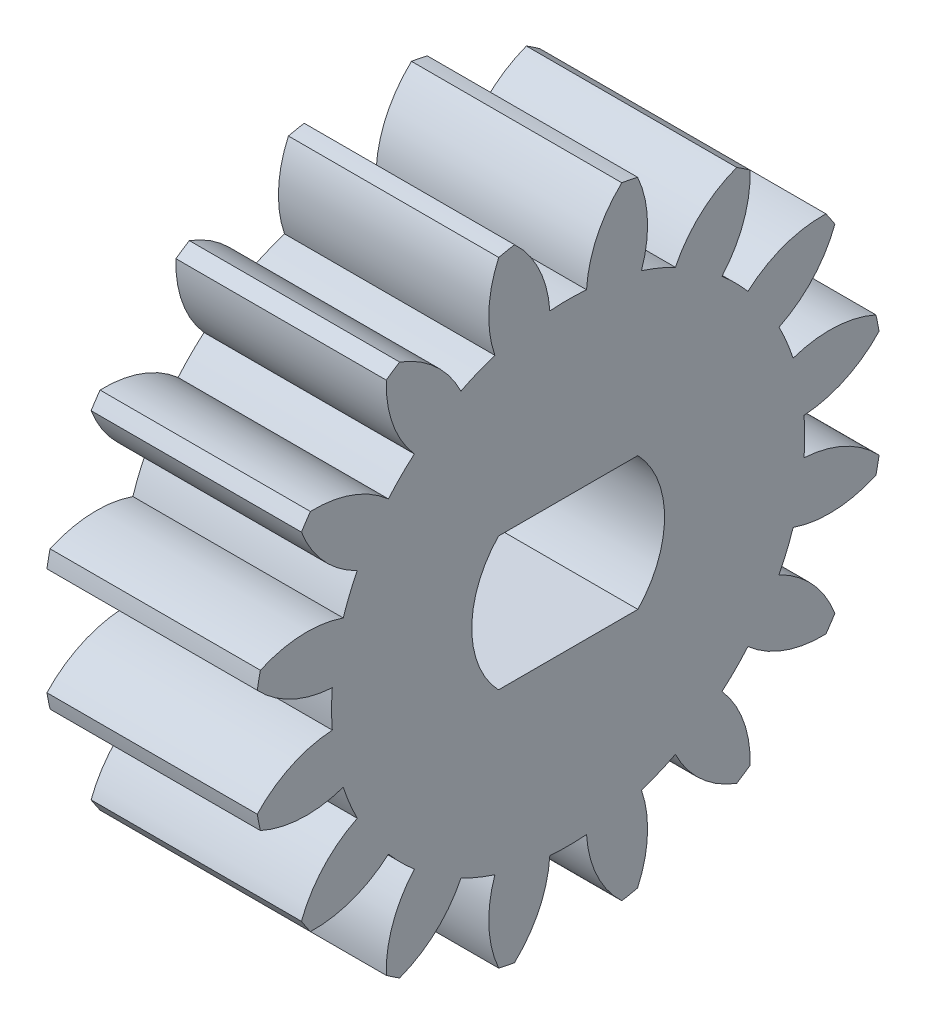
SolidWorks part; units mm, degrees
ref_plane "Plane1" through (0, 0, 0) normal (0, 0, 1) x (1, 0, 0)
ref_plane "Plane2" through (0, 0, 0) normal (0, 1, 0) x (1, 0, 0)
ref_plane "Plane3" through (0, 0, 0) normal (1, 0, 0) x (0, 0, -1)
sketch "HoldingSke" plane through (0, 0, 0) normal (0, 1, 0) x (1, 0, 0)
  line L0 (0, 0) -> (0.9613, -0.2756)
  line L1 (-15, 0) -> (100, 0) construction
  line L2 (0, 0) -> (-2.1039, 2.3779)
  line L3 (0, 0) -> (-11.863, 4.5341)
  line L4 (0, 0) -> (8.3015, 2.3804)
  line L5 (0, 0) -> (-46.8476, -17.4728)
  line L6 (0, 0) -> (-4.9738, -3.3558)
  line L7 (-2.1039, 2.3779) -> (8.6586, 51.2059)
  line L8 (-76.2, 54.61) -> (-75.9, 54.61)
  line L9 (-71.009, 38.7566) -> (-53.1078, 45.2721)
  line L10 (-76.2, 71.12) -> (104.1128, 71.12)
  line L11 (0, 0) -> (-6, 0)
  line L12 (-76.2, 101.6) -> (-76.162, 101.6)
  line L13 (24.9733, 27.94) -> (52.9518, 28.4284)
  line L14 (24.9733, 27.94) -> (24.9743, 27.94)
  line L15 (24.9733, 27.94) -> (100.4006, 29.5858)
  line L16 (-63.627, -1) -> (-12.827, -1)
  circle A0 centre (0, 0) radius 1
  circle A1 centre (0, 0) radius 6.749
  circle A2 centre (0, 0) radius 37.5
  circle A3 centre (0, 0) radius 1
  dimension "MHD" = 13.498
  dimension "Hub_dia" = 75
  dimension "Bore" = 2
  dimension "MBD" = 2
  dimension "Num_teeth" = 16
  dimension "Pitch" = 1
  dimension "Overall_len" = 50
  dimension "Show_teeth" = 16
  dimension "Thickness" = 6
  dimension "OAL" = 50.0001
  dimension "T_dim" = 0.3
  dimension "Ap" = 20
  dimension "H" = 19.05
  dimension "Pitch_radius" = 180.3128
  dimension "Width" = 6
  dimension "Backlash" = 0.038
  dimension "Addendum_fac" = 1
  dimension "Dedendum_fac" = 1.25
  dimension "Clearance_fac" = 0.25
  dimension "Dedendum_add" = 0.001
  dimension "Module" = 1
sketch "BasProSke" plane through (0, 0, 0) normal (0, 1, 0) x (1, 0, 0)
  line L0 (-10, 0) -> (60, 0) construction
  line L1 (0, 0) -> (0, 9)
  line L2 (0, 0) -> (6, 0)
  line L3 (6, 0) -> (6, 9)
  line L4 (6, 9) -> (0, 9)
  dimension "Thickness" = 6
  dimension "Diameter" = 18
revolve "Base-Revolve" add sketch "BasProSke" angle 360 about L0
sketch "TooCutSke" plane through (0, 0, 0) normal (1, 0, 0) x (0, 0, -1)
  line L1 (0, 0) -> (0, 107) construction
  line L2 (0, 0) -> (-0.8506, 7.9547) construction
  line L3 (0, 0) -> (-3.1089, 15.6293) construction
  line L4 (-0.8506, 7.9547) -> (-1.5544, 7.8146) construction
  arc A0 (0.5238, 6.7286) -> (-0.5238, 6.7286) centre (0, 0) ccw
  arc A1 (1.5534, 8.8907) -> (-1.5534, 8.8907) centre (0, 0) ccw
  circle A2 centre (0, 0) radius 8 construction
  circle A3 centre (0, 0) radius 7.5175 construction
  arc A4 (-0.5238, 6.7286) -> (-1.5534, 8.8907) centre (-3.7179, 6.5338) ccw
  arc A5 (1.5534, 8.8907) -> (0.5238, 6.7286) centre (3.7179, 6.5338) ccw
  dimension "Root_dia" = 13.498
  dimension "Overcut_dia" = 18.0508
  dimension "Pitch_dia" = 16
  dimension "Base_dia" = 15.0351
  dimension "Flank_rad" = 3.2
  dimension "Half_ang" = 11.25
  dimension "Half_CT" = 0.7176
extrude "ToothCut" cut sketch "TooCutSke" along normal through all
fillet "Breaks" [suppressed] radius 0.02 tangent propagation no
fillet "RootFillets" [suppressed] radius 0.251
pattern_circular "TeethCuts" count 16 every 22.5 about axis through (-10, 0, 0) along (1, 0, 0) of "ToothCut", "RootFillets", "Breaks"
sketch "HubNeaOneSke" plane through (0, 0, 0) normal (-1, 0, 0) x (0, 0, 1)
  circle A0 centre (0, 0) radius 6.749
  dimension "Diameter" = 13.498
extrude "HubNearOne" [suppressed] add sketch "HubNeaOneSke" along normal blind 44.0001
sketch "HubNeaBotSke" plane through (0, 0, 0) normal (-1, 0, 0) x (0, 0, 1)
  circle A0 centre (0, 0) radius 6.749
  dimension "Diameter" = 13.498
extrude "HubNearBoth" [suppressed] add sketch "HubNeaBotSke" along normal blind 22.0001
ref_plane "FarPln" through (6, 0, 0) normal (1, 0, 0) x (0, 0, -1)
sketch "HubFarSke" plane through (6, 0, 0) normal (1, 0, 0) x (0, 0, -1)
  circle A0 centre (0, 0) radius 6.749
  dimension "Diameter" = 13.498
extrude "HubFar" [suppressed] add sketch "HubFarSke" along normal blind 22.0001
sketch "BorSke" plane through (0, 0, 0) normal (1, 0, 0) x (0, 0, -1)
  line L0 (-1.9881, 1.9) -> (1.9881, 1.9)
  line L1 (-1.9881, -1.9) -> (1.9881, -1.9)
  circle A0 centre (0, 0) radius 2.75
  point P6 (0, 1.9)
  dimension "D1" = 1.9
  dimension "Diameter" = 5.5
  dimension "D2" = 1.9
sketch "KeySke" plane through (0, 0, 0) normal (1, 0, 0) x (0, 0, -1)
  line L0 (-0.4, 0) -> (-0.4, 1.3)
  line L1 (-0.4, 1.3) -> (0.4, 1.3)
  line L2 (0.4, 1.3) -> (0.4, 0)
  line L3 (0, 0) -> (0, 34) construction
  line L4 (-0.4, 0) -> (0.4, 0)
  dimension "Offset" = 1.3
  dimension "Width" = 0.8
extrude "Cut-Extrude1" cut sketch "BorSke" along normal blind 13 contours L0 A0 L1 region at (0, 0, 0)
extrude "Keyway" [suppressed] cut sketch "KeySke" along normal mid plane 100.0002
pattern_circular "Keyway2" [suppressed] count 2 every 90 about axis through (-10, 0, 0) along (1, 0, 0) reverse direction yes
equation "' \"Module@HoldingSke\" = 6.35"
equation "' \"Num_teeth@HoldingSke\" = 12"
equation "' \"Ap@HoldingSke\" =  20"
equation "' \"Ap@HoldingSke\" = 20"
equation "' \"Width@HoldingSke\" = 0.5 * 25.4"
equation "' \"Hub_dia@HoldingSke\"= 1 * 25.4"
equation "' \"Hub_dia@HoldingSke\" = 1 * 25.4"
equation "' \"Overall_len@HoldingSke\" = 1.0 * 25.4"
equation "' \"Bore@HoldingSke\" = 0.75 * 25.4"
equation "' \"T_dim@HoldingSke\" = 0.1 * 25.4"
equation "' \"Width@KeySke\" = 0.25 * 25.4"
equation "' \"Show_teeth@HoldingSke\" = 13"
equation "' \"Backlash@HoldingSke\" = 0.009 * 25.4"
equation "' \"Addendum_fac@HoldingSke\" = 1.0"
equation "' \"Dedendum_fac@HoldingSke\" = 1.25"
equation "' \"Dedendum_add@HoldingSke\" = 0.00005 * 25.4"
equation "' \"Clearance_fac@HoldingSke\" = 0.25"
equation "\"Pitch@HoldingSke\" = 1 / \"Module@HoldingSke\""
equation "\"Overcut_dia@TooCutSke\" = (\"Num_teeth@HoldingSke\" + 2 * \"Addendum_fac@HoldingSke\") / \"Pitch@HoldingSke\" + 0.002 * 25.4"
equation "\"Pitch_dia@TooCutSke\" = \"Num_teeth@HoldingSke\" / \"Pitch@HoldingSke\""
equation "\"Base_dia@TooCutSke\" = \"Num_teeth@HoldingSke\" / \"Pitch@HoldingSke\" * cos((\"Ap@HoldingSke\"  * 3.14159265 / 180))"
equation "\"Root_dia@TooCutSke\" = (\"Num_teeth@HoldingSke\" + 2) / \"Pitch@HoldingSke\" - 2 * (\"Addendum_fac@HoldingSke\" + \"Dedendum_fac@HoldingSke\") / \"Pitch@HoldingSke\" - \"Dedendum_add@HoldingSke\" * 2"
equation "\"Half_ang@TooCutSke\" = 180 / \"Num_teeth@HoldingSke\""
equation "\"Half_CT@TooCutSke\" = \"Num_teeth@HoldingSke\" / \"Pitch@HoldingSke\" * sin((3.14159265 / 2 / \"Num_teeth@HoldingSke\")) / 2 - 7 * \"Backlash@HoldingSke\" / 4"
equation "\"Flank_rad@TooCutSke\" = \"Num_teeth@HoldingSke\" / \"Pitch@HoldingSke\" / 5"
equation "\"Radius@RootFillets\" = \"Clearance_fac@HoldingSke\" / \"Pitch@HoldingSke\" + \"Dedendum_add@HoldingSke\""
equation "\"Break_rad@Breaks\" = 0.02 / \"Pitch@HoldingSke\""
equation "\"Thickness@HoldingSke\" = \"Width@HoldingSke\""
equation "\"OAL@HoldingSke\" = \"Thickness@HoldingSke\""
equation "\"MHD@HoldingSke\" = (\"Num_teeth@HoldingSke\" + 2) / \"Pitch@HoldingSke\" - 2 * (\"Addendum_fac@HoldingSke\" + \"Dedendum_fac@HoldingSke\")  / \"Pitch@HoldingSke\" - \"Dedendum_add@HoldingSke\" * 2"
equation "\"MBD@HoldingSke\" = (\"Num_teeth@HoldingSke\" + 2) / \"Pitch@HoldingSke\" - 2 * (\"Addendum_fac@HoldingSke\" + \"Dedendum_fac@HoldingSke\")  / \"Pitch@HoldingSke\" - \"Dedendum_add@HoldingSke\" * 2 - 0.002 * 25.4"
equation "\"MHD@HoldingSke\" = ((sgn( \"MHD@HoldingSke\" - \"Hub_dia@HoldingSke\" )-1)*( \"MHD@HoldingSke\" - \"Hub_dia@HoldingSke\" ))/-2+ \"Hub_dia@HoldingSke\""
equation "\"MBD@HoldingSke\" = ((sgn( \"MBD@HoldingSke\" - \"Bore@HoldingSke\" )-1)*( \"MBD@HoldingSke\" - \"Bore@HoldingSke\" ))/-2+ \"Bore@HoldingSke\""
equation "\"OAL@HoldingSke\" = ((sgn( \"OAL@HoldingSke\" - \"Overall_len@HoldingSke\" )+1)*( \"OAL@HoldingSke\" - \"Overall_len@HoldingSke\" ))/2 + \"Overall_len@HoldingSke\" + 0.000002 * 25.4"
equation "\"Num_teeth@TeethCuts\" = int( \"Show_teeth@HoldingSke\" ) + 1"
equation "\"Num_teeth@TeethCuts\" = ((sgn( \"Num_teeth@TeethCuts\" - \"Num_teeth@HoldingSke\" )-1)*( \"Num_teeth@TeethCuts\" - \"Num_teeth@HoldingSke\" ))/-2+ \"Num_teeth@HoldingSke\""
equation "\"Num_teeth@TeethCuts\" = ((sgn( \"Num_teeth@TeethCuts\" - 2.0)+1)*( \"Num_teeth@TeethCuts\" - 2.0))/2 +2.0"
equation "\"Angle@TeethCuts\" = 360.0 / \"Num_teeth@HoldingSke\""
equation "\"Diameter@BasProSke\" = (\"Num_teeth@HoldingSke\" + 2 * \"Addendum_fac@HoldingSke\") / \"Pitch@HoldingSke\""
equation "\"Thickness@BasProSke\"  = \"Thickness@HoldingSke\""
equation "' \"Fillet_rad@BasProSke\" =  \"Thickness@HoldingSke\" * 0.05"
equation "' \"Fillet_rad@BasProSke\" = \"Thickness@HoldingSke\" * 0.05"
equation "\"MHD@HoldingSke\" = ((sgn( \"MHD@HoldingSke\" - \"Root_dia@TooCutSke\" )-1)*( \"MHD@HoldingSke\" - \"Root_dia@TooCutSke\" ))/-2+ \"Root_dia@TooCutSke\""
equation "\"Diameter@HubNeaOneSke\" = \"MHD@HoldingSke\""
equation "\"Length@HubNearOne\" = \"OAL@HoldingSke\" - \"Thickness@BasProSke\""
equation "\"Diameter@HubNeaBotSke\" = \"MHD@HoldingSke\""
equation "\"Length@HubNearBoth\" = ( \"OAL@HoldingSke\" - \"Thickness@BasProSke\" ) / 2.0"
equation "\"Thickness@FarPln\" = \"Thickness@BasProSke\""
equation "\"Diameter@HubFarSke\" = \"MHD@HoldingSke\""
equation "\"Length@HubFar\" = ( \"OAL@HoldingSke\" - \"Thickness@BasProSke\" ) / 2.0"
equation "\"D1@Keyway\" = \"OAL@HoldingSke\" * 2.0"
equation "\"Offset@KeySke\" = \"T_dim@HoldingSke\" + \"MBD@HoldingSke\" / 2.0"
